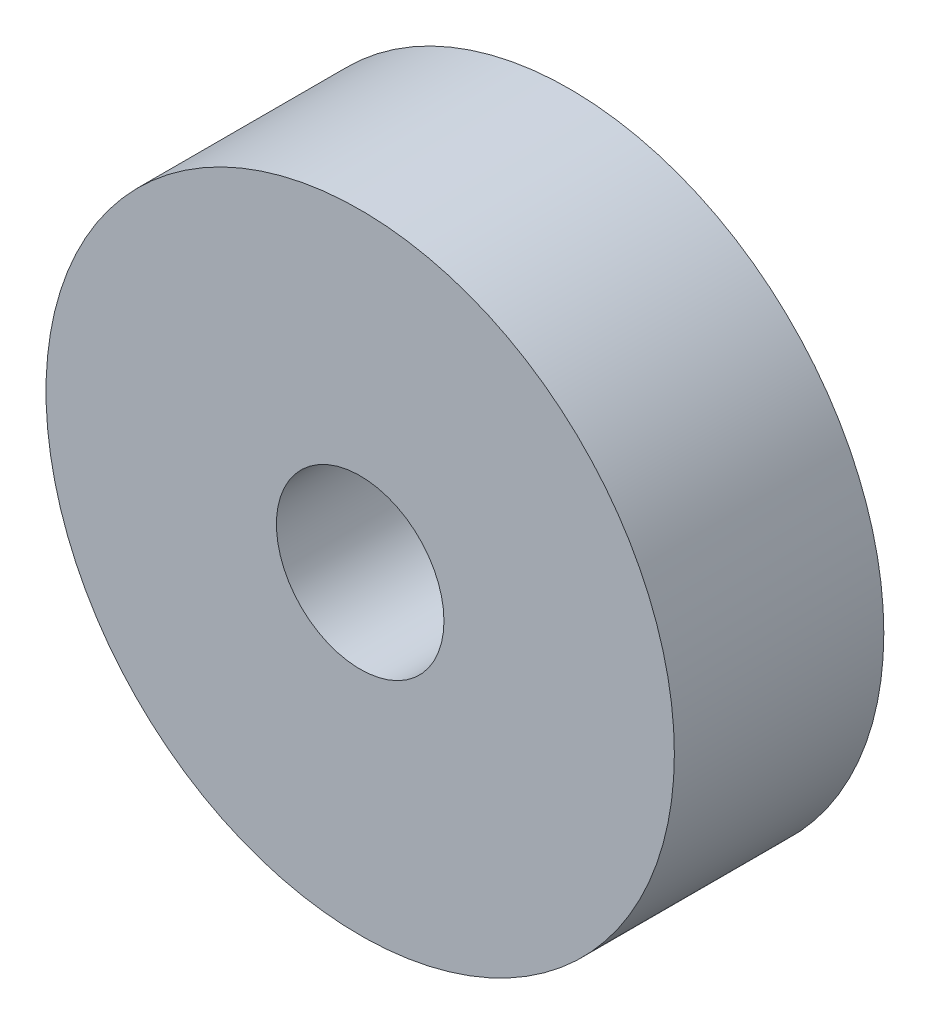
SolidWorks part; units mm, degrees
material "Copper"
ref_plane "Front Plane" through (0, 0, 0) normal (0, 0, 1) x (1, 0, 0)
ref_plane "Top Plane" through (0, 0, 0) normal (0, 1, 0) x (1, 0, 0)
ref_plane "Right Plane" through (0, 0, 0) normal (1, 0, 0) x (0, 0, -1)
sketch "Sketch1" plane through (0, 0, 0) normal (0, 0, 1) x (1, 0, 0)
  circle A0 centre (0, 0) radius 15
  circle A1 centre (0, 0) radius 4
  dimension "D1" = 30
  dimension "D2" = 8
extrude "Boss-Extrude1" add sketch "Sketch1" along normal blind 10
